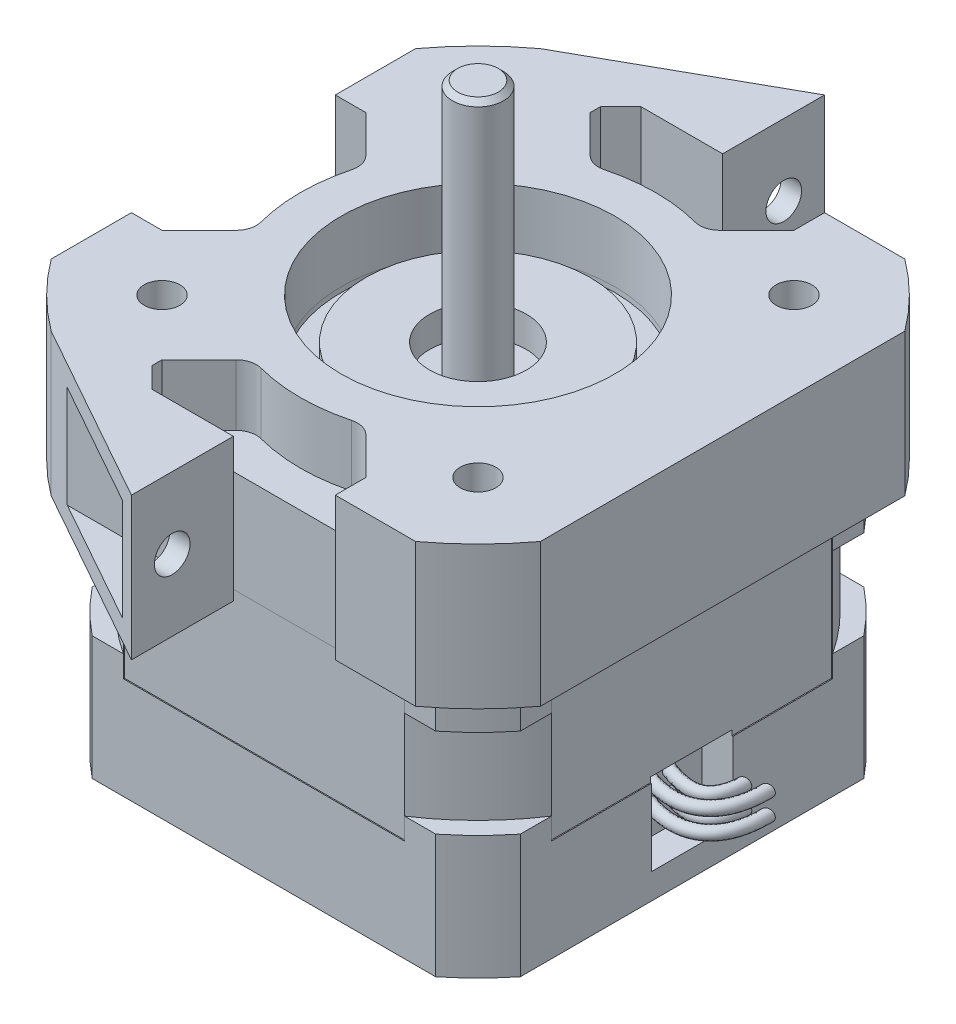
SolidWorks part; units mm, degrees
ref_plane "Front Plane" through (0, 0, 0) normal (0, 0, 1) x (1, 0, 0)
ref_plane "Top Plane" through (0, 0, 0) normal (0, 1, 0) x (1, 0, 0)
ref_plane "Right Plane" through (0, 0, 0) normal (1, 0, 0) x (0, 0, -1)
sketch "Sketch1" plane through (0, 0, 0) normal (0, 1, 0) x (1, 0, 0)
  line L0 (0, -21) -> (0, 21) construction
  line L1 (-21, 16.851) -> (-21, -16.851)
  line L2 (-16.851, -21) -> (16.851, -21)
  line L3 (21, -16.851) -> (21, 16.851)
  line L4 (16.851, 21) -> (-16.851, 21)
  line L5 (-21, 0) -> (21, 0) construction
  arc A0 (-21, 16.851) -> (-16.851, 21) centre (0, 0) cw
  arc A1 (16.851, 21) -> (21, 16.851) centre (0, 0) cw
  arc A2 (21, -16.851) -> (16.851, -21) centre (0, 0) cw
  arc A3 (-21, -16.851) -> (-16.851, -21) centre (0, 0) ccw
  dimension "D3" = 26.925
  dimension "D1" = 42
  dimension "D2" = 42
extrude "Boss-Extrude2" add sketch "Sketch1" along normal blind 33
sketch "Sketch3" plane through (0, 0, 0) normal (0, 0, 1) x (1, 0, 0)
  line L0 (0, -2.0131) -> (0, 34.8611) construction
  line L1 (-30.125, 20.875) -> (-25.125, 20.875)
  line L2 (-30.125, 20.875) -> (-30.125, 12.125)
  line L3 (-30.125, 12.125) -> (-25.125, 12.125)
  line L4 (-25.125, 20.875) -> (-25.125, 12.125)
  line L5 (21, 16.5) -> (-21, 16.5) construction
  line L6 (21, 33) -> (21, 0) construction
  line L7 (-21, 33) -> (-21, 0) construction
  point P13 (-25.125, 16.5)
  dimension "D1" = 8.75
  dimension "D2" = 25.125
  dimension "D3" = 5
revolve "Cut-Revolve1" cut sketch "Sketch3" angle 360 about L0
sketch "Sketch4" plane through (0, 33, 0) normal (0, 1, 0) x (1, 0, 0)
  circle A0 centre (0, 0) radius 13.425
  dimension "D1" = 26.85
extrude "Cut-Extrude1" cut sketch "Sketch4" against normal blind 0.5
sketch "Sketch5" plane through (0, 32.5, 0) normal (0, 1, 0) x (1, 0, 0)
  circle A0 centre (0, 0) radius 11
  dimension "D1" = 22
extrude "Boss-Extrude3" add sketch "Sketch5" along normal blind 2.5
sketch "Sketch6" plane through (0, 35, 0) normal (0, 1, 0) x (1, 0, 0)
  circle A0 centre (0, 0) radius 4.75
  dimension "D1" = 9.5
extrude "Cut-Extrude2" cut sketch "Sketch6" against normal blind 3
sketch "Sketch7" plane through (0, 32, 0) normal (0, 1, 0) x (1, 0, 0)
  circle A0 centre (0, 0) radius 2.5
  dimension "D1" = 5
extrude "Boss-Extrude4" add sketch "Sketch7" along normal blind 25.25
chamfer "Chamfer1" distance 0.5 angle 45 1 edges at (0, 57.25, 2.5)
sketch "Sketch8" plane through (0, 0, 0) normal (0, -1, 0) x (1, 0, 0)
  circle A0 centre (0, 0) radius 4.5
  dimension "D1" = 9
extrude "Cut-Extrude3" cut sketch "Sketch8" against normal blind 3
sketch "Sketch9" plane through (0, 33, 0) normal (0, 1, 0) x (1, 0, 0)
  line L0 (-15.5, 15.5) -> (15.5, 15.5) construction
  line L1 (15.5, 15.5) -> (15.5, -15.5) construction
  line L2 (15.5, -15.5) -> (-15.5, -15.5) construction
  line L3 (-15.5, -15.5) -> (-15.5, 15.5) construction
  point P2 (-15.5, 0)
  point P5 (0, 15.5)
  dimension "D1" = 31
  dimension "D2" = 31
hole_wizard "M3x0.5 Tapped Hole1" positions "Sketch11" profile "Sketch10" tap size "M3x0.5" standard "ANSI Metric"
sketch "Sketch11" plane through (0, 33, 0) normal (0, 1, 0) x (1, 0, 0)
  point P0 (-15.5, -15.5)
  point P3 (-15.5, 15.5)
  point P6 (15.5, 15.5)
  point P9 (15.5, -15.5)
sketch "Sketch10" plane through (-15.5, 33, 15.5) normal (1, 0, 0) x (0, 0, 1)
  line L0 (0, 0) -> (0, 5.2511)
  line L1 (0, 5.2511) -> (1.25, 4.5)
  line L2 (1.25, 4.5) -> (1.25, 0)
  line L5 (1.25, 0) -> (0, 0)
  line L10 (0, 5.2511) -> (-1.25, 4.5) construction
  line L11 (0, -6.35) -> (0, 107.95) construction
  dimension "Tap Drill Dia." = 2.5
  dimension "Tap Drill Depth" = 4.5
  dimension "Drill Angle" = 118
sketch "Sketch12" plane through (21, 0, 0) normal (1, 0, 0) x (0, 0, -1)
  line L0 (-16.851, 0) -> (16.851, 0) construction
  line L1 (-4, 10.5) -> (4, 10.5)
  line L2 (-4, 10.5) -> (-4, 2.5)
  line L3 (-4, 2.5) -> (4, 2.5)
  line L4 (4, 10.5) -> (4, 2.5)
  point P4 (0, 2.5)
  dimension "D1" = 8
  dimension "D2" = 8
  dimension "D3" = 2.5
extrude "Cut-Extrude4" cut sketch "Sketch12" against normal blind 3
sketch "Sketch13" plane through (18, 0, 0) normal (1, 0, 0) x (0, 0, -1)
  circle A0 centre (-1.1125, 7.415) radius 0.6
  circle A1 centre (0.707, 7.415) radius 0.6
  circle A2 centre (-1.1125, 5.3322) radius 0.6
  circle A3 centre (0.707, 5.3322) radius 0.6
  dimension "D1" = 1.2
sketch "Sketch14" plane through (0, 0, 0) normal (0, 1, 0) x (1, 0, 0)
  spline S0 degree 2 poles (17.6767, 0) (23.6461, -2.3668) (23.7984, 3.3576) knots 0 0 0 1 1 1
sweep "Sweep2" add profiles "Sketch13" path "Sketch14"
sketch "Sketch15" plane through (0, 0, -21) normal (0, 0, -1) x (-1, 0, 0)
  line L0 (-13.7937, 12.125) -> (-13.7937, 20.875) construction
  line L1 (-13.7937, 23) -> (13.7937, 23)
  line L2 (-13.7937, 23) -> (-13.7937, 10)
  line L3 (-13.7937, 10) -> (13.7937, 10)
  line L4 (13.7937, 23) -> (13.7937, 10)
  line L5 (13.7937, 20.875) -> (13.7937, 12.125) construction
  point P8 (-13.7937, 16.5)
  point P9 (-13.7937, 16.5)
  dimension "D1" = 13
extrude "Cut-Extrude5" cut sketch "Sketch15" against normal blind 0.1
ref_axis "Axis1" through (0, 0, 0) along (0, 1, 0)
pattern_circular "CirPattern1" count 4 over 360 about axis through (0, 0, 0) along (0, 1, 0) of "Cut-Extrude5"
ref_plane "Plane1" through (0, 33, 0) normal (0, 1, 0) x (1, 0, 0)
sketch "Sketch16" plane through (0, 33, 0) normal (0, 1, 0) x (1, 0, 0)
  line L0 (-10.001, -21) -> (-5.5264, -16.5254)
  line L1 (9.999, -21) -> (5.5249, -16.5259)
  line L2 (-21, -9.999) -> (-16.5259, -5.5249)
  line L3 (-16.5254, 5.5264) -> (-21, 10.001)
  line L4 (-21, 16.851) -> (-21, -16.851)
  line L5 (-16.851, -21) -> (16.851, -21)
  line L6 (21, -16.851) -> (21, 16.851)
  line L7 (16.851, 21) -> (-16.851, 21)
  line L8 (-21, 16.851) -> (-21, -16.851)
  line L9 (-16.851, -21) -> (16.851, -21)
  line L10 (21, -16.851) -> (21, 16.851)
  line L11 (16.851, 21) -> (-16.851, 21)
  line L12 (-10.001, 21) -> (-5.5264, 16.5254)
  line L13 (9.999, 21) -> (5.5249, 16.5259)
  circle A0 centre (0, 0) radius 13.425 construction
  circle A1 centre (0, 0) radius 13.425
  arc A4 (-16.851, 21) -> (-21, 16.851) centre (0, 0) ccw
  arc A5 (-21, -16.851) -> (-16.851, -21) centre (0, 0) ccw
  arc A6 (16.851, -21) -> (21, -16.851) centre (0, 0) ccw
  arc A7 (21, 16.851) -> (16.851, 21) centre (0, 0) ccw
  arc A8 (-16.851, 21) -> (-21, 16.851) centre (0, 0) ccw
  arc A9 (-21, -16.851) -> (-16.851, -21) centre (0, 0) ccw
  arc A10 (16.851, -21) -> (21, -16.851) centre (0, 0) ccw
  arc A11 (21, 16.851) -> (16.851, 21) centre (0, 0) ccw
  circle A12 centre (-15.5, -15.5) radius 1.25 construction
  circle A13 centre (15.5, -15.5) radius 1.25 construction
  circle A14 centre (15.5, 15.5) radius 1.25 construction
  circle A15 centre (-15.5, 15.5) radius 1.25 construction
  circle A16 centre (-15.5, -15.5) radius 1.25
  circle A17 centre (15.5, -15.5) radius 1.25
  circle A18 centre (15.5, 15.5) radius 1.25
  circle A19 centre (-15.5, 15.5) radius 1.25
  circle A20 centre (-15.5, 15.5) radius 1.75
  circle A21 centre (-15.5, -15.5) radius 1.75
  circle A22 centre (15.5, -15.5) radius 1.75
  circle A23 centre (15.5, 15.5) radius 1.75
  circle A24 centre (0, 0) radius 17.425
  dimension "D4" = 20
  dimension "D5" = 45
  dimension "D6" = 45
  dimension "D7" = 6.85
  dimension "D8" = 45
  dimension "D9" = 45
  dimension "D10" = 20
  dimension "D11" = 6.85
  dimension "D12" = 45
  dimension "D13" = 45
  dimension "D14" = 20
  dimension "D15" = 6.85
  dimension "D1" = 0
  dimension "D2" = 0.5
  dimension "D3" = 4
extrude "Boss-Extrude5" add sketch "Sketch16" along normal blind 6 separate body contours A24 L2 L8 A9 L9 L0 A21 | A24 A1 | A24 L12 L11 A8 L8 L3 A20 | A24 L1 L9 A10 L10 A11 L11 L13 A23 A22 region at (-13.426, 33, 20.7812) region at (-11.9734, 33, 11.9723) region at (8.0785, 33, 18.4465) region at (-18.608, 33, -7.9184)
sketch "Sketch17" plane through (0, 39, 0) normal (0, 1, 0) x (1, 0, 0)
  line L13 (-21, 10.001) -> (-24, 10.001)
  line L14 (-10.001, 21) -> (-10.001, 24)
  line L15 (9.999, 21) -> (9.999, 24)
  line L16 (-21, -9.999) -> (-24, -9.999)
  line L17 (-10.001, -21) -> (-10.001, -24)
  line L18 (9.999, -21) -> (9.999, -24)
  line L26 (-8.7583, -24) -> (-4.6476, -19.8892)
  line L27 (4.646, -19.8896) -> (8.7564, -24)
  line L28 (8.7564, -24) -> (17.8747, -24)
  line L29 (24, -17.8747) -> (24, 17.8747)
  line L30 (17.8747, 24) -> (8.7564, 24)
  line L31 (8.7564, 24) -> (4.646, 19.8896)
  line L32 (-4.6476, 19.8892) -> (-8.7583, 24)
  line L33 (-8.7583, 24) -> (-17.8747, 24)
  line L34 (-24, 17.8747) -> (-24, 8.7583)
  line L35 (-24, 8.7583) -> (-19.8892, 4.6476)
  line L36 (-19.8896, -4.646) -> (-24, -8.7564)
  line L37 (-24, -8.7564) -> (-24, -17.8747)
  line L38 (-17.8747, -24) -> (-8.7583, -24)
  line L39 (-8.7583, -24) -> (-4.6476, -19.8892)
  line L40 (4.646, -19.8896) -> (8.7564, -24)
  line L41 (8.7564, -24) -> (17.8747, -24)
  line L42 (24, -17.8747) -> (24, 17.8747)
  line L43 (17.8747, 24) -> (8.7564, 24)
  line L44 (8.7564, 24) -> (4.646, 19.8896)
  line L45 (-4.6476, 19.8892) -> (-8.7583, 24)
  line L46 (-8.7583, 24) -> (-17.8747, 24)
  line L47 (-24, 17.8747) -> (-24, 8.7583)
  line L48 (-24, 8.7583) -> (-19.8892, 4.6476)
  line L49 (-19.8896, -4.646) -> (-24, -8.7564)
  line L50 (-24, -8.7564) -> (-24, -17.8747)
  line L51 (-17.8747, -24) -> (-8.7583, -24)
  line L71 (-9.7939, -21.5) -> (-5.3895, -17.0956)
  line L72 (5.388, -17.0961) -> (9.7919, -21.5)
  line L73 (9.7919, -21.5) -> (17.0259, -21.5)
  line L74 (21.5, -17.0259) -> (21.5, 17.0259)
  line L75 (17.0259, 21.5) -> (9.7919, 21.5)
  line L76 (9.7919, 21.5) -> (5.388, 17.0961)
  line L77 (-5.3895, 17.0956) -> (-9.7939, 21.5)
  line L78 (-9.7939, 21.5) -> (-17.0259, 21.5)
  line L79 (-21.5, 17.0259) -> (-21.5, 9.7939)
  line L80 (-21.5, 9.7939) -> (-17.0956, 5.3895)
  line L81 (-17.0961, -5.388) -> (-21.5, -9.7919)
  line L82 (-21.5, -9.7919) -> (-21.5, -17.0259)
  line L83 (-17.0259, -21.5) -> (-9.7939, -21.5)
  line L84 (-9.7939, -21.5) -> (-5.3895, -17.0956)
  line L85 (5.388, -17.0961) -> (9.7919, -21.5)
  line L86 (9.7919, -21.5) -> (17.0259, -21.5)
  line L87 (21.5, -17.0259) -> (21.5, 17.0259)
  line L88 (17.0259, 21.5) -> (9.7919, 21.5)
  line L89 (9.7919, 21.5) -> (5.388, 17.0961)
  line L90 (-5.3895, 17.0956) -> (-9.7939, 21.5)
  line L91 (-9.7939, 21.5) -> (-17.0259, 21.5)
  line L92 (-21.5, 17.0259) -> (-21.5, 9.7939)
  line L93 (-21.5, 9.7939) -> (-17.0956, 5.3895)
  line L94 (-17.0961, -5.388) -> (-21.5, -9.7919)
  line L95 (-21.5, -9.7919) -> (-21.5, -17.0259)
  line L96 (-17.0259, -21.5) -> (-9.7939, -21.5)
  arc A14 (-4.6476, -19.8892) -> (4.646, -19.8896) centre (0, 0) ccw
  arc A15 (17.8747, -24) -> (24, -17.8747) centre (0, 0) ccw
  arc A16 (24, 17.8747) -> (17.8747, 24) centre (0, 0) ccw
  arc A17 (4.646, 19.8896) -> (-4.6476, 19.8892) centre (0, 0) ccw
  arc A18 (-17.8747, 24) -> (-24, 17.8747) centre (0, 0) ccw
  arc A19 (-19.8892, 4.6476) -> (-19.8896, -4.646) centre (0, 0) ccw
  arc A20 (-24, -17.8747) -> (-17.8747, -24) centre (0, 0) ccw
  arc A21 (-4.6476, -19.8892) -> (4.646, -19.8896) centre (0, 0) ccw
  arc A22 (17.8747, -24) -> (24, -17.8747) centre (0, 0) ccw
  arc A23 (24, 17.8747) -> (17.8747, 24) centre (0, 0) ccw
  arc A24 (4.646, 19.8896) -> (-4.6476, 19.8892) centre (0, 0) ccw
  arc A25 (-17.8747, 24) -> (-24, 17.8747) centre (0, 0) ccw
  arc A26 (-19.8892, 4.6476) -> (-19.8896, -4.646) centre (0, 0) ccw
  arc A27 (-24, -17.8747) -> (-17.8747, -24) centre (0, 0) ccw
  arc A36 (-5.3895, -17.0956) -> (5.388, -17.0961) centre (0, 0) ccw
  arc A37 (17.0259, -21.5) -> (21.5, -17.0259) centre (0, 0) ccw
  arc A38 (21.5, 17.0259) -> (17.0259, 21.5) centre (0, 0) ccw
  arc A39 (5.388, 17.0961) -> (-5.3895, 17.0956) centre (0, 0) ccw
  arc A40 (-17.0259, 21.5) -> (-21.5, 17.0259) centre (0, 0) ccw
  arc A41 (-17.0956, 5.3895) -> (-17.0961, -5.388) centre (0, 0) ccw
  arc A42 (-21.5, -17.0259) -> (-17.0259, -21.5) centre (0, 0) ccw
  arc A43 (-5.3895, -17.0956) -> (5.388, -17.0961) centre (0, 0) ccw
  arc A44 (17.0259, -21.5) -> (21.5, -17.0259) centre (0, 0) ccw
  arc A45 (21.5, 17.0259) -> (17.0259, 21.5) centre (0, 0) ccw
  arc A46 (5.388, 17.0961) -> (-5.3895, 17.0956) centre (0, 0) ccw
  arc A47 (-17.0259, 21.5) -> (-21.5, 17.0259) centre (0, 0) ccw
  arc A48 (-17.0956, 5.3895) -> (-17.0961, -5.388) centre (0, 0) ccw
  arc A49 (-21.5, -17.0259) -> (-17.0259, -21.5) centre (0, 0) ccw
  line M24 (9.999, -21) -> (16.851, -21)
  arc M25 (16.851, -21) -> (21, -16.851) centre (0, 0) ccw
  line M26 (21, -16.851) -> (21, 16.851)
  arc M27 (21, 16.851) -> (16.851, 21) centre (0, 0) ccw
  line M28 (16.851, 21) -> (9.999, 21)
  line M32 (-10.001, 21) -> (-16.851, 21)
  arc M33 (-16.851, 21) -> (-21, 16.851) centre (0, 0) ccw
  line M34 (-21, 16.851) -> (-21, 10.001)
  line M38 (-21, -9.999) -> (-21, -16.851)
  arc M39 (-21, -16.851) -> (-16.851, -21) centre (0, 0) ccw
  line M40 (-16.851, -21) -> (-10.001, -21)
  dimension "D1" = 3
  dimension "D2" = 0.5
extrude "Boss-Extrude6" add sketch "Sketch17" against normal blind 14 separate body contours L46 A25 L47 L13 L14 M34 M33 M32 | L50 A27 L51 L17 L16 M40 M39 M38 | L42 A23 L43 L15 L18 L41 A22 M28 M27 M26 M25 M24 region at (-22.75, 39, -10.199) region at (-21.698, 39, 13.5124) region at (10.499, 39, -22.75)
fillet "Fillet1" radius 2 6 edges at (5.5249, 36, 16.5259) (-5.5264, 36, 16.5254) (-16.5259, 36, 5.5249) (-16.5254, 36, -5.5264) (5.5249, 36, -16.5259) (-5.5264, 36, -16.5254)
extrude "Boss-Extrude7" add sketch "Sketch17<4>" against normal up to vertex (6 mm away) separate body contours L95 A49 L96 L17 L16 M40 M39 M38 | L91 A47 L92 L13 L14 M34 M33 M32 | L87 A45 L88 L15 L18 L86 A44 M28 M27 M26 M25 M24 region at (-21.25, 39, -10.1636) region at (-21.25, 39, 10.1617) region at (13.5124, 39, -21.0549) up to point (-17.3686, 33, 6.3676)
sketch "Sketch17<4>" plane through (0, 39, 0) normal (0, 1, 0) x (1, 0, 0) same geometry as "Sketch17"
combine bodies "Combine2" operation type add bodies to combine 115 122 121 114 116 117 120
sketch "Sketch18" plane through (0, 39, 0) normal (0, 1, 0) x (1, 0, 0)
  line L0 (-10.001, 24) -> (-0.001, 24)
  line L1 (-0.001, 24) -> (-0.001, 34)
  line L3 (-17.8747, 24) -> (-0.001, 34)
  line L4 (-17.8747, -24) -> (-0.001, -24)
  line L5 (-10.001, -21) -> (-10.001, -24) construction
  line L6 (-0.001, -24) -> (-0.001, -34)
  line L7 (-0.001, -34) -> (-17.8747, -24)
  line L23 (9.999, 24) -> (9.999, 21)
  line L24 (9.999, 21) -> (6.3676, 17.3686)
  line L25 (-6.3692, 17.3682) -> (-10.001, 21)
  line L26 (-10.001, 21) -> (-10.001, 24)
  line L27 (-10.001, 24) -> (-17.8747, 24)
  line L28 (-24, 17.8747) -> (-24, 10.001)
  line L29 (-24, 10.001) -> (-21, 10.001)
  line L30 (-21, 10.001) -> (-17.3682, 6.3692)
  line L31 (-17.3686, -6.3676) -> (-21, -9.999)
  line L32 (-21, -9.999) -> (-24, -9.999)
  line L33 (-24, -9.999) -> (-24, -17.8747)
  line L34 (-17.8747, -24) -> (-10.001, -24)
  line L35 (-10.001, -24) -> (-10.001, -21)
  line L36 (-10.001, -21) -> (-6.3692, -17.3682)
  line L37 (6.3676, -17.3686) -> (9.999, -21)
  line L38 (9.999, -21) -> (9.999, -24)
  line L39 (9.999, -24) -> (17.8747, -24)
  line L40 (24, -17.8747) -> (24, 17.8747)
  line L41 (17.8747, 24) -> (9.999, 24)
  line L46 (-10.001, 24) -> (-17.8747, 24)
  arc A15 (4.4434, 16.8489) -> (6.3676, 17.3686) centre (4.9534, 18.7828) ccw
  arc A16 (4.4434, 16.8489) -> (-4.4448, 16.8486) centre (0, 0) ccw
  arc A17 (-6.3692, 17.3682) -> (-4.4448, 16.8486) centre (-4.955, 18.7824) ccw
  arc A18 (-17.8747, 24) -> (-24, 17.8747) centre (0, 0) ccw
  arc A19 (-16.8486, 4.4448) -> (-17.3682, 6.3692) centre (-18.7824, 4.955) ccw
  arc A20 (-16.8486, 4.4448) -> (-16.8489, -4.4434) centre (0, 0) ccw
  arc A21 (-17.3686, -6.3676) -> (-16.8489, -4.4434) centre (-18.7828, -4.9534) ccw
  arc A22 (-24, -17.8747) -> (-17.8747, -24) centre (0, 0) ccw
  arc A23 (-4.4448, -16.8486) -> (-6.3692, -17.3682) centre (-4.955, -18.7824) ccw
  arc A24 (-4.4448, -16.8486) -> (4.4434, -16.8489) centre (0, 0) ccw
  arc A25 (6.3676, -17.3686) -> (4.4434, -16.8489) centre (4.9534, -18.7828) ccw
  arc A26 (17.8747, -24) -> (24, -17.8747) centre (0, 0) ccw
  arc A27 (24, 17.8747) -> (17.8747, 24) centre (0, 0) ccw
  dimension "D3" = 10
  dimension "D1" = 10
  dimension "D2" = 10
  dimension "D4" = 10
  dimension "D5" = 0
extrude "Boss-Extrude8" add sketch "Sketch18" against normal up to surface (14 mm away) up to face at (-18.2819, 25, -18.2819)
sketch "Sketch19" plane through (-0.001, 0, 0) normal (1, 0, 0) x (0, 0, -1)
  line L0 (34, 25) -> (34, 39) construction
  line L1 (34, 27) -> (26, 27)
  line L2 (34, 27) -> (34, 37)
  line L3 (34, 37) -> (26, 37)
  line L4 (26, 27) -> (26, 37)
  line L5 (24, 39) -> (34, 39) construction
  line L6 (-34, 25) -> (-34, 39) construction
  line L7 (-34, 37) -> (-26, 37)
  line L8 (-34, 37) -> (-34, 27)
  line L9 (-34, 27) -> (-26, 27)
  line L10 (-26, 37) -> (-26, 27)
  line L11 (-34, 39) -> (-24, 39) construction
  circle A0 centre (30, 32) radius 1.75
  circle A1 centre (-30, 32) radius 1.75
  point P18 (0, 0)
  point P19 (34, 32)
  point P20 (-34, 32)
  point P21 (30, 27)
  point P24 (0, 0)
  point P25 (-30, 27)
  dimension "D7" = 3.5
  dimension "D8" = 3.5
  dimension "D1" = 10
  dimension "D2" = 2
  dimension "D3" = 8
  dimension "D4" = 8
  dimension "D5" = 10
  dimension "D6" = 2
ref_plane "Plane2" through (-2.001, 0, 0) normal (1, 0, 0) x (0, 0, -1)
sketch "Sketch20" plane through (-2.001, 0, 0) normal (1, 0, 0) x (0, 0, -1)
  line L0 (34, 27) -> (34, 37) construction
  line L1 (34, 37) -> (26, 37) construction
  line L2 (34, 27) -> (26, 27) construction
  line L3 (26, 27) -> (26, 37) construction
  line L4 (-34, 37) -> (-34, 27) construction
  line L5 (-34, 37) -> (-26, 37) construction
  line L6 (-26, 37) -> (-26, 27) construction
  line L7 (-34, 27) -> (-26, 27) construction
  line L8 (34, 27) -> (34, 37)
  line L9 (34, 37) -> (26, 37)
  line L10 (34, 27) -> (26, 27)
  line L11 (26, 27) -> (26, 37)
  line L12 (-34, 37) -> (-34, 27)
  line L13 (-34, 37) -> (-26, 37)
  line L14 (-26, 37) -> (-26, 27)
  line L15 (-34, 27) -> (-26, 27)
  circle A0 centre (-30, 32) radius 1.75 construction
  circle A1 centre (30, 32) radius 1.75 construction
  circle A2 centre (-30, 32) radius 1.75
  circle A3 centre (30, 32) radius 1.75
extrude "Cut-Extrude7" cut sketch "Sketch20" against normal blind 34 contours L12 L15 L14 L13 A2 | A2 | L10 L11 L9 L8 region at (-2.001, 36.8719, 30)
chamfer "Chamfer2" distance 2 angle 45 2 edges at (-10.001, 32, 24) (-10.001, 32, -24)
ref_plane "Plane3" [suppressed] through (-2.001, 37, 32.881) normal (0, 0, 1) x (1, 0, 0)
extrude "Cut-Extrude10" cut sketch "Sketch19" against normal blind 10 contours A0 | A1
